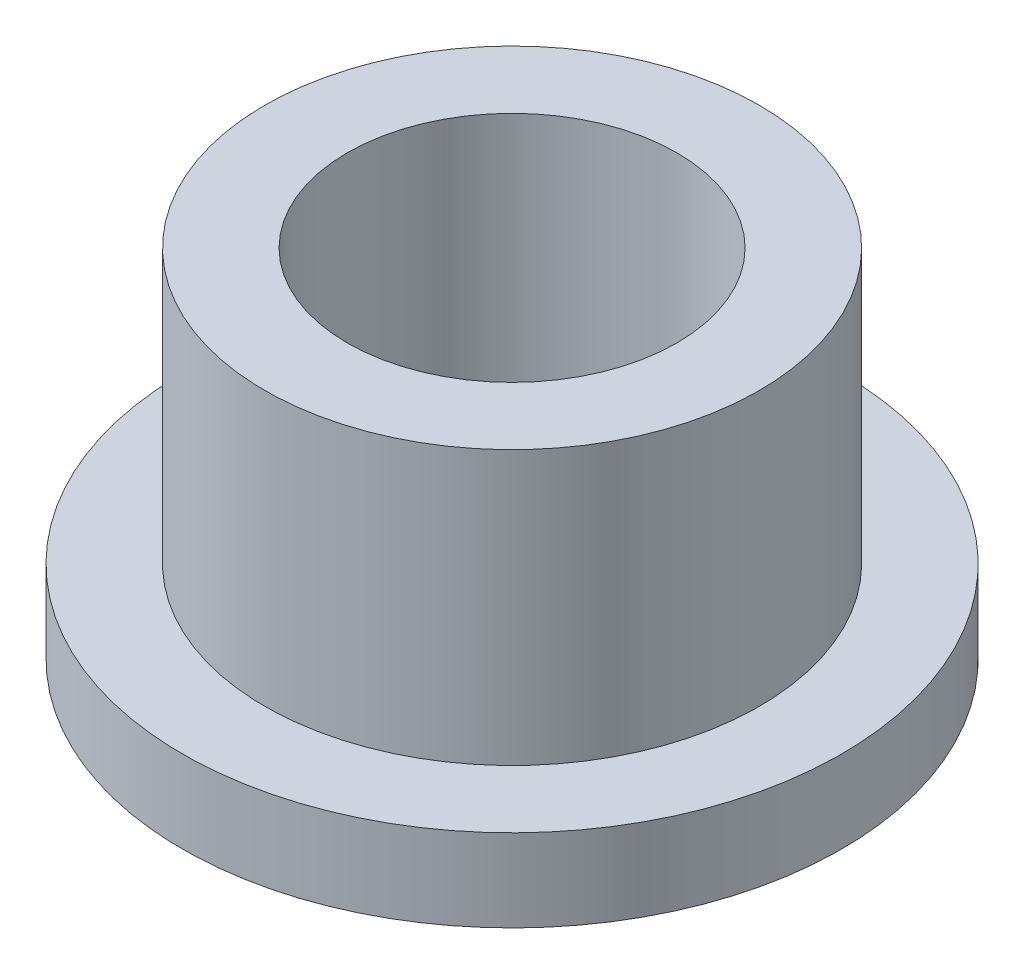
SolidWorks part; units mm, degrees
material "Brass"
ref_plane "Front Plane" through (0, 0, 0) normal (0, 0, 1) x (1, 0, 0)
ref_plane "Top Plane" through (0, 0, 0) normal (0, 1, 0) x (1, 0, 0)
ref_plane "Right Plane" through (0, 0, 0) normal (1, 0, 0) x (0, 0, -1)
sketch "Sketch1" plane through (0, 0, 0) normal (0, 0, 1) x (1, 0, 0)
  line L0 (3.175, 0) -> (6.35, 0)
  line L1 (6.35, 0) -> (6.35, 1.5875)
  line L2 (6.35, 1.5875) -> (4.7625, 1.5875)
  line L3 (4.7625, 1.5875) -> (4.7625, 6.858)
  line L4 (4.7625, 6.858) -> (3.175, 6.858)
  line L5 (3.175, 6.858) -> (3.175, 0)
  line L6 (0, 0) -> (0, 40.9931) construction
  dimension "D1" = 6.35
  dimension "D2" = 9.525
  dimension "D3" = 12.7
  dimension "D4" = 1.5875
  dimension "D5" = 6.858
revolve "Revolve1" add sketch "Sketch1" angle 360 about L6
